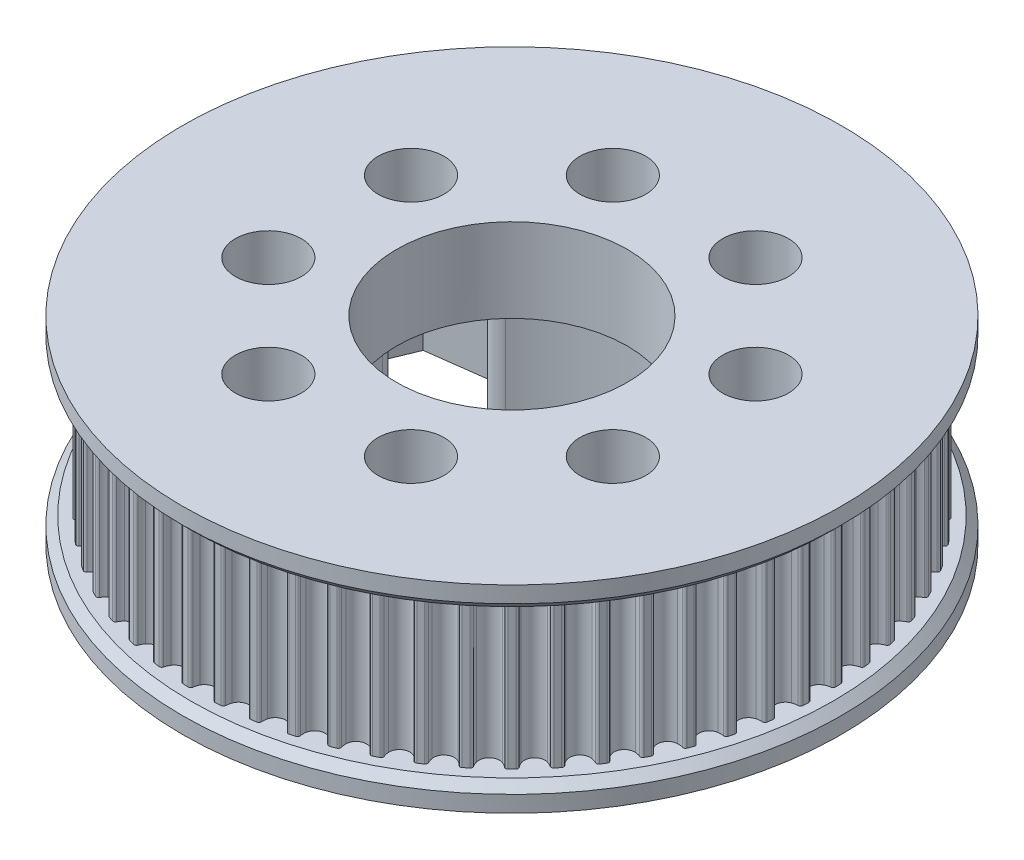
SolidWorks part; units mm, degrees
ref_plane "Front Plane" through (0, 0, 0) normal (0, 0, 1) x (1, 0, 0)
ref_plane "Top Plane" through (0, 0, 0) normal (0, 1, 0) x (1, 0, 0)
ref_plane "Right Plane" through (0, 0, 0) normal (1, 0, 0) x (0, 0, -1)
sketch "Sketch2" plane through (0, 0, 0) normal (0, 1, 0) x (1, 0, 0)
  arc A0 (0, -20) -> (0, 20) centre (0, 0) ccw
  arc A1 (0, 20) -> (0, -20) centre (0, 0) ccw
  arc A2 (-0.1312, 18.0334) -> (0, 18.0196) centre (0, 18.6496) ccw
  arc A3 (-1.8836, 17.9209) -> (-1.3573, 18.3322) centre (-1.9494, 18.5474) ccw
  arc A4 (-1.3573, 18.3322) -> (-1.2932, 18.6645) centre (-2.3677, 18.6994) ccw
  arc A5 (-0.6648, 18.6974) -> (-0.7174, 18.7921) centre (-0.8134, 18.6769) ccw
  arc A6 (-1.1525, 18.8093) -> (-1.2509, 18.7641) centre (-1.1433, 18.6596) ccw
  arc A7 (-1.2509, 18.7641) -> (-1.2932, 18.6645) centre (-1.1433, 18.6596) ccw
  arc A8 (-0.82, 18.8267) -> (-1.1525, 18.8093) centre (0, 0) ccw
  arc A9 (-0.7174, 18.7921) -> (-0.82, 18.8267) centre (-0.8134, 18.6769) ccw
  arc A10 (-0.6648, 18.6974) -> (-0.5664, 18.3737) centre (0.4001, 18.8445) ccw
  arc A11 (-0.5664, 18.3737) -> (-0.1312, 18.0334) centre (0, 18.6496) ccw
  arc A12 (1.7545, 17.9483) -> (1.8836, 17.9209) centre (1.9494, 18.5474) ccw
  arc A13 (0, 18.0196) -> (0.5664, 18.3737) centre (0, 18.6496) ccw
  arc A14 (0.5664, 18.3737) -> (0.6648, 18.6974) centre (-0.4001, 18.8445) ccw
  arc A15 (1.2932, 18.6645) -> (1.2509, 18.7641) centre (1.1433, 18.6596) ccw
  arc A16 (0.82, 18.8267) -> (0.7174, 18.7921) centre (0.8134, 18.6769) ccw
  arc A17 (0.7174, 18.7921) -> (0.6648, 18.6974) centre (0.8134, 18.6769) ccw
  arc A18 (1.1525, 18.8093) -> (0.82, 18.8267) centre (0, 0) ccw
  arc A19 (1.2509, 18.7641) -> (1.1525, 18.8093) centre (1.1433, 18.6596) ccw
  arc A20 (1.2932, 18.6645) -> (1.3573, 18.3322) centre (2.3677, 18.6994) ccw
  arc A21 (1.3573, 18.3322) -> (1.7545, 17.9483) centre (1.9494, 18.5474) ccw
  arc A22 (3.621, 17.6666) -> (3.7465, 17.6258) centre (3.8775, 18.2421) ccw
  arc A23 (1.8836, 17.9209) -> (2.4838, 18.2138) centre (1.9494, 18.5474) ccw
  arc A24 (2.4838, 18.2138) -> (2.6156, 18.5255) centre (1.5719, 18.7831) ccw
  arc A25 (3.2371, 18.4271) -> (3.2054, 18.5306) centre (3.0875, 18.4379) ccw
  arc A26 (2.7834, 18.6379) -> (2.6777, 18.6142) centre (2.7612, 18.4895) ccw
  arc A27 (2.6777, 18.6142) -> (2.6156, 18.5255) centre (2.7612, 18.4895) ccw
  arc A28 (3.1123, 18.5858) -> (2.7834, 18.6379) centre (0, 0) ccw
  arc A29 (3.2054, 18.5306) -> (3.1123, 18.5858) centre (3.0875, 18.4379) ccw
  arc A30 (3.2371, 18.4271) -> (3.2661, 18.0899) centre (4.3093, 18.3495) ccw
  arc A31 (3.2661, 18.0899) -> (3.621, 17.6666) centre (3.8775, 18.2421) ccw
  arc A32 (5.4478, 17.1913) -> (5.5684, 17.1377) centre (5.763, 17.7368) ccw
  arc A33 (3.7465, 17.6258) -> (4.3741, 17.8544) centre (3.8775, 18.2421) ccw
  arc A34 (4.3741, 17.8544) -> (4.5377, 18.1506) centre (3.5267, 18.5159) ccw
  arc A35 (5.1455, 17.9877) -> (5.1248, 18.094) centre (4.9979, 18.0141) ccw
  arc A36 (4.7163, 18.2449) -> (4.6088, 18.2323) centre (4.6788, 18.0996) ccw
  arc A37 (4.6088, 18.2323) -> (4.5377, 18.1506) centre (4.6788, 18.0996) ccw
  arc A38 (5.038, 18.1587) -> (4.7163, 18.2449) centre (0, 0) ccw
  arc A39 (5.1248, 18.094) -> (5.038, 18.1587) centre (4.9979, 18.0141) ccw
  arc A40 (5.1455, 17.9877) -> (5.1391, 17.6494) centre (6.2037, 17.7985) ccw
  arc A41 (5.1391, 17.6494) -> (5.4478, 17.1913) centre (5.763, 17.7368) ccw
  arc A42 (7.215, 16.5277) -> (7.3292, 16.4617) centre (7.5855, 17.0373) ccw
  arc A43 (5.5684, 17.1377) -> (6.2164, 17.2994) centre (5.763, 17.7368) ccw
  arc A44 (6.2164, 17.2994) -> (6.4101, 17.5768) centre (5.4428, 18.0458) ccw
  arc A45 (6.9976, 17.3513) -> (6.9881, 17.4592) centre (6.8535, 17.393) ccw
  arc A46 (6.5976, 17.6519) -> (6.4893, 17.6507) centre (6.5451, 17.5114) ccw
  arc A47 (6.4893, 17.6507) -> (6.4101, 17.5768) centre (6.5451, 17.5114) ccw
  arc A48 (6.9085, 17.5326) -> (6.5976, 17.6519) centre (0, 0) ccw
  arc A49 (6.9881, 17.4592) -> (6.9085, 17.5326) centre (6.8535, 17.393) ccw
  arc A50 (6.9976, 17.3513) -> (6.9558, 17.0156) centre (8.0302, 17.0526) ccw
  arc A51 (6.9558, 17.0156) -> (7.215, 16.5277) centre (7.5855, 17.0373) ccw
  arc A52 (8.9031, 15.683) -> (9.0098, 15.6054) centre (9.3248, 16.151) ccw
  arc A53 (7.3292, 16.4617) -> (7.9907, 16.5548) centre (7.5855, 17.0373) ccw
  arc A54 (7.9907, 16.5548) -> (8.2123, 16.8105) centre (7.2993, 17.378) ccw
  arc A55 (8.7729, 16.5248) -> (8.7748, 16.6331) centre (8.634, 16.5814) ccw
  arc A56 (8.4066, 16.8656) -> (8.2988, 16.8757) centre (8.3397, 16.7313) ccw
  arc A57 (8.2988, 16.8757) -> (8.2123, 16.8105) centre (8.3397, 16.7313) ccw
  arc A58 (8.7033, 16.7144) -> (8.4066, 16.8656) centre (0, 0) ccw
  arc A59 (8.7748, 16.6331) -> (8.7033, 16.7144) centre (8.634, 16.5814) ccw
  arc A60 (8.7729, 16.5248) -> (8.6964, 16.1953) centre (9.7687, 16.1198) ccw
  arc A61 (8.6964, 16.1953) -> (8.9031, 15.683) centre (9.3248, 16.151) ccw
  arc A62 (10.4936, 14.6665) -> (10.5917, 14.5782) centre (10.962, 15.0878) ccw
  arc A63 (9.0098, 15.6054) -> (9.6773, 15.6289) centre (9.3248, 16.151) ccw
  arc A64 (9.6773, 15.6289) -> (9.9245, 15.86) centre (9.0758, 16.5198) ccw
  arc A65 (10.4522, 15.5173) -> (10.4654, 15.6248) centre (10.3199, 15.588) ccw
  arc A66 (10.1235, 15.8945) -> (10.0173, 15.9157) centre (10.0429, 15.7679) ccw
  arc A67 (10.0173, 15.9157) -> (9.9245, 15.86) centre (10.0429, 15.7679) ccw
  arc A68 (10.4027, 15.7131) -> (10.1235, 15.8945) centre (0, 0) ccw
  arc A69 (10.4654, 15.6248) -> (10.4027, 15.7131) centre (10.3199, 15.588) ccw
  arc A70 (10.4522, 15.5173) -> (10.3416, 15.1975) centre (11.4002, 15.0104) ccw
  arc A71 (10.3416, 15.1975) -> (10.4936, 14.6665) centre (10.962, 15.0878) ccw
  arc A72 (11.9692, 13.4892) -> (12.0575, 13.3912) centre (12.479, 13.8593) ccw
  arc A73 (10.5917, 14.5782) -> (11.258, 14.5317) centre (10.962, 15.0878) ccw
  arc A74 (11.258, 14.5317) -> (11.5279, 14.7357) centre (10.7529, 15.4806) ccw
  arc A75 (12.0169, 14.3397) -> (12.0413, 14.4453) centre (11.8928, 14.4239) ccw
  arc A76 (11.7294, 14.7492) -> (11.6261, 14.7815) centre (11.6361, 14.6318) ccw
  arc A77 (11.6261, 14.7815) -> (11.5279, 14.7357) centre (11.6361, 14.6318) ccw
  arc A78 (11.9882, 14.5397) -> (11.7294, 14.7492) centre (0, 0) ccw
  arc A79 (12.0413, 14.4453) -> (11.9882, 14.5397) centre (11.8928, 14.4239) ccw
  arc A80 (12.0169, 14.3397) -> (11.8735, 14.0333) centre (12.9067, 13.7365) ccw
  arc A81 (11.8735, 14.0333) -> (11.9692, 13.4892) centre (12.479, 13.8593) ccw
  arc A82 (13.3136, 12.1642) -> (13.3912, 12.0575) centre (13.8593, 12.479) ccw
  arc A83 (12.0575, 13.3912) -> (12.7153, 13.2753) centre (12.479, 13.8593) ccw
  arc A84 (12.7153, 13.2753) -> (13.0051, 13.45) centre (12.3121, 14.2719) ccw
  arc A85 (13.45, 13.0051) -> (13.4852, 13.1075) centre (13.3353, 13.1018) ccw
  arc A86 (13.2069, 13.4423) -> (13.1075, 13.4852) centre (13.1018, 13.3353) ccw
  arc A87 (13.1075, 13.4852) -> (13.0051, 13.45) centre (13.1018, 13.3353) ccw
  arc A88 (13.4423, 13.2069) -> (13.2069, 13.4423) centre (0, 0) ccw
  arc A89 (13.4852, 13.1075) -> (13.4423, 13.2069) centre (13.3353, 13.1018) ccw
  arc A90 (13.45, 13.0051) -> (13.2753, 12.7153) centre (14.2719, 12.3121) ccw
  arc A91 (13.2753, 12.7153) -> (13.3136, 12.1642) centre (13.8593, 12.479) ccw
  arc A92 (14.5122, 10.7059) -> (14.5782, 10.5917) centre (15.0878, 10.962) ccw
  arc A93 (13.3912, 12.0575) -> (14.0333, 11.8735) centre (13.8593, 12.479) ccw
  arc A94 (14.0333, 11.8735) -> (14.3397, 12.0169) centre (13.7365, 12.9067) ccw
  arc A95 (14.7357, 11.5279) -> (14.7815, 11.6261) centre (14.6318, 11.6361) ccw
  arc A96 (14.5397, 11.9882) -> (14.4453, 12.0413) centre (14.4239, 11.8928) ccw
  arc A97 (14.4453, 12.0413) -> (14.3397, 12.0169) centre (14.4239, 11.8928) ccw
  arc A98 (14.7492, 11.7294) -> (14.5397, 11.9882) centre (0, 0) ccw
  arc A99 (14.7815, 11.6261) -> (14.7492, 11.7294) centre (14.6318, 11.6361) ccw
  arc A100 (14.7357, 11.5279) -> (14.5317, 11.258) centre (15.4806, 10.7529) ccw
  arc A101 (14.5317, 11.258) -> (14.5122, 10.7059) centre (15.0878, 10.962) ccw
  arc A102 (15.5518, 9.1304) -> (15.6054, 9.0098) centre (16.151, 9.3248) ccw
  arc A103 (14.5782, 10.5917) -> (15.1975, 10.3416) centre (15.0878, 10.962) ccw
  arc A104 (15.1975, 10.3416) -> (15.5173, 10.4522) centre (15.0104, 11.4002) ccw
  arc A105 (15.86, 9.9245) -> (15.9157, 10.0173) centre (15.7679, 10.0429) ccw
  arc A106 (15.7131, 10.4027) -> (15.6248, 10.4654) centre (15.588, 10.3199) ccw
  arc A107 (15.6248, 10.4654) -> (15.5173, 10.4522) centre (15.588, 10.3199) ccw
  arc A108 (15.8945, 10.1235) -> (15.7131, 10.4027) centre (0, 0) ccw
  arc A109 (15.9157, 10.0173) -> (15.8945, 10.1235) centre (15.7679, 10.0429) ccw
  arc A110 (15.86, 9.9245) -> (15.6289, 9.6773) centre (16.5198, 9.0758) ccw
  arc A111 (15.6289, 9.6773) -> (15.5518, 9.1304) centre (16.151, 9.3248) ccw
  arc A112 (16.421, 7.4547) -> (16.4617, 7.3292) centre (17.0373, 7.5855) ccw
  arc A113 (15.6054, 9.0098) -> (16.1953, 8.6964) centre (16.151, 9.3248) ccw
  arc A114 (16.1953, 8.6964) -> (16.5248, 8.7729) centre (16.1198, 9.7687) ccw
  arc A115 (16.8105, 8.2123) -> (16.8757, 8.2988) centre (16.7313, 8.3397) ccw
  arc A116 (16.7144, 8.7033) -> (16.6331, 8.7748) centre (16.5814, 8.634) ccw
  arc A117 (16.6331, 8.7748) -> (16.5248, 8.7729) centre (16.5814, 8.634) ccw
  arc A118 (16.8656, 8.4066) -> (16.7144, 8.7033) centre (0, 0) ccw
  arc A119 (16.8757, 8.2988) -> (16.8656, 8.4066) centre (16.7313, 8.3397) ccw
  arc A120 (16.8105, 8.2123) -> (16.5548, 7.9907) centre (17.378, 7.2993) ccw
  arc A121 (16.5548, 7.9907) -> (16.421, 7.4547) centre (17.0373, 7.5855) ccw
  arc A122 (17.1102, 5.6974) -> (17.1377, 5.5684) centre (17.7368, 5.763) ccw
  arc A123 (16.4617, 7.3292) -> (17.0156, 6.9558) centre (17.0373, 7.5855) ccw
  arc A124 (17.0156, 6.9558) -> (17.3513, 6.9976) centre (17.0526, 8.0302) ccw
  arc A125 (17.5768, 6.4101) -> (17.6507, 6.4893) centre (17.5114, 6.5451) ccw
  arc A126 (17.5326, 6.9085) -> (17.4592, 6.9881) centre (17.393, 6.8535) ccw
  arc A127 (17.4592, 6.9881) -> (17.3513, 6.9976) centre (17.393, 6.8535) ccw
  arc A128 (17.6519, 6.5976) -> (17.5326, 6.9085) centre (0, 0) ccw
  arc A129 (17.6507, 6.4893) -> (17.6519, 6.5976) centre (17.5114, 6.5451) ccw
  arc A130 (17.5768, 6.4101) -> (17.2994, 6.2164) centre (18.0458, 5.4428) ccw
  arc A131 (17.2994, 6.2164) -> (17.1102, 5.6974) centre (17.7368, 5.763) ccw
  arc A132 (17.6121, 3.8777) -> (17.6258, 3.7465) centre (18.2421, 3.8775) ccw
  arc A133 (17.1377, 5.5684) -> (17.6494, 5.1391) centre (17.7368, 5.763) ccw
  arc A134 (17.6494, 5.1391) -> (17.9877, 5.1455) centre (17.7985, 6.2037) ccw
  arc A135 (18.1506, 4.5377) -> (18.2323, 4.6088) centre (18.0996, 4.6788) ccw
  arc A136 (18.1587, 5.038) -> (18.094, 5.1248) centre (18.0141, 4.9979) ccw
  arc A137 (18.094, 5.1248) -> (17.9877, 5.1455) centre (18.0141, 4.9979) ccw
  arc A138 (18.2449, 4.7163) -> (18.1587, 5.038) centre (0, 0) ccw
  arc A139 (18.2323, 4.6088) -> (18.2449, 4.7163) centre (18.0996, 4.6788) ccw
  arc A140 (18.1506, 4.5377) -> (17.8544, 4.3741) centre (18.5159, 3.5267) ccw
  arc A141 (17.8544, 4.3741) -> (17.6121, 3.8777) centre (18.2421, 3.8775) ccw
  arc A142 (17.9209, 2.0155) -> (17.9209, 1.8836) centre (18.5474, 1.9494) ccw
  arc A143 (17.6258, 3.7465) -> (18.0899, 3.2661) centre (18.2421, 3.8775) ccw
  arc A144 (18.0899, 3.2661) -> (18.4271, 3.2371) centre (18.3495, 4.3093) ccw
  arc A145 (18.5255, 2.6156) -> (18.6142, 2.6777) centre (18.4895, 2.7612) ccw
  arc A146 (18.5858, 3.1123) -> (18.5306, 3.2054) centre (18.4379, 3.0875) ccw
  arc A147 (18.5306, 3.2054) -> (18.4271, 3.2371) centre (18.4379, 3.0875) ccw
  arc A148 (18.6379, 2.7834) -> (18.5858, 3.1123) centre (0, 0) ccw
  arc A149 (18.6142, 2.6777) -> (18.6379, 2.7834) centre (18.4895, 2.7612) ccw
  arc A150 (18.5255, 2.6156) -> (18.2138, 2.4838) centre (18.7831, 1.5719) ccw
  arc A151 (18.2138, 2.4838) -> (17.9209, 2.0155) centre (18.5474, 1.9494) ccw
  arc A152 (18.0334, 0.1312) -> (18.0196, 0) centre (18.6496, 0) ccw
  arc A153 (17.9209, 1.8836) -> (18.3322, 1.3573) centre (18.5474, 1.9494) ccw
  arc A154 (18.3322, 1.3573) -> (18.6645, 1.2932) centre (18.6994, 2.3677) ccw
  arc A155 (18.6974, 0.6648) -> (18.7921, 0.7174) centre (18.6769, 0.8134) ccw
  arc A156 (18.8093, 1.1525) -> (18.7641, 1.2509) centre (18.6596, 1.1433) ccw
  arc A157 (18.7641, 1.2509) -> (18.6645, 1.2932) centre (18.6596, 1.1433) ccw
  arc A158 (18.8267, 0.82) -> (18.8093, 1.1525) centre (0, 0) ccw
  arc A159 (18.7921, 0.7174) -> (18.8267, 0.82) centre (18.6769, 0.8134) ccw
  arc A160 (18.6974, 0.6648) -> (18.3737, 0.5664) centre (18.8445, -0.4001) ccw
  arc A161 (18.3737, 0.5664) -> (18.0334, 0.1312) centre (18.6496, 0) ccw
  arc A162 (17.9483, -1.7545) -> (17.9209, -1.8836) centre (18.5474, -1.9494) ccw
  arc A163 (18.0196, 0) -> (18.3737, -0.5664) centre (18.6496, 0) ccw
  arc A164 (18.3737, -0.5664) -> (18.6974, -0.6648) centre (18.8445, 0.4001) ccw
  arc A165 (18.6645, -1.2932) -> (18.7641, -1.2509) centre (18.6596, -1.1433) ccw
  arc A166 (18.8267, -0.82) -> (18.7921, -0.7174) centre (18.6769, -0.8134) ccw
  arc A167 (18.7921, -0.7174) -> (18.6974, -0.6648) centre (18.6769, -0.8134) ccw
  arc A168 (18.8093, -1.1525) -> (18.8267, -0.82) centre (0, 0) ccw
  arc A169 (18.7641, -1.2509) -> (18.8093, -1.1525) centre (18.6596, -1.1433) ccw
  arc A170 (18.6645, -1.2932) -> (18.3322, -1.3573) centre (18.6994, -2.3677) ccw
  arc A171 (18.3322, -1.3573) -> (17.9483, -1.7545) centre (18.5474, -1.9494) ccw
  arc A172 (17.6666, -3.621) -> (17.6258, -3.7465) centre (18.2421, -3.8775) ccw
  arc A173 (17.9209, -1.8836) -> (18.2138, -2.4838) centre (18.5474, -1.9494) ccw
  arc A174 (18.2138, -2.4838) -> (18.5255, -2.6156) centre (18.7831, -1.5719) ccw
  arc A175 (18.4271, -3.2371) -> (18.5306, -3.2054) centre (18.4379, -3.0875) ccw
  arc A176 (18.6379, -2.7834) -> (18.6142, -2.6777) centre (18.4895, -2.7612) ccw
  arc A177 (18.6142, -2.6777) -> (18.5255, -2.6156) centre (18.4895, -2.7612) ccw
  arc A178 (18.5858, -3.1123) -> (18.6379, -2.7834) centre (0, 0) ccw
  arc A179 (18.5306, -3.2054) -> (18.5858, -3.1123) centre (18.4379, -3.0875) ccw
  arc A180 (18.4271, -3.2371) -> (18.0899, -3.2661) centre (18.3495, -4.3093) ccw
  arc A181 (18.0899, -3.2661) -> (17.6666, -3.621) centre (18.2421, -3.8775) ccw
  arc A182 (17.1913, -5.4478) -> (17.1377, -5.5684) centre (17.7368, -5.763) ccw
  arc A183 (17.6258, -3.7465) -> (17.8544, -4.3741) centre (18.2421, -3.8775) ccw
  arc A184 (17.8544, -4.3741) -> (18.1506, -4.5377) centre (18.5159, -3.5267) ccw
  arc A185 (17.9877, -5.1455) -> (18.094, -5.1248) centre (18.0141, -4.9979) ccw
  arc A186 (18.2449, -4.7163) -> (18.2323, -4.6088) centre (18.0996, -4.6788) ccw
  arc A187 (18.2323, -4.6088) -> (18.1506, -4.5377) centre (18.0996, -4.6788) ccw
  arc A188 (18.1587, -5.038) -> (18.2449, -4.7163) centre (0, 0) ccw
  arc A189 (18.094, -5.1248) -> (18.1587, -5.038) centre (18.0141, -4.9979) ccw
  arc A190 (17.9877, -5.1455) -> (17.6494, -5.1391) centre (17.7985, -6.2037) ccw
  arc A191 (17.6494, -5.1391) -> (17.1913, -5.4478) centre (17.7368, -5.763) ccw
  arc A192 (16.5277, -7.215) -> (16.4617, -7.3292) centre (17.0373, -7.5855) ccw
  arc A193 (17.1377, -5.5684) -> (17.2994, -6.2164) centre (17.7368, -5.763) ccw
  arc A194 (17.2994, -6.2164) -> (17.5768, -6.4101) centre (18.0458, -5.4428) ccw
  arc A195 (17.3513, -6.9976) -> (17.4592, -6.9881) centre (17.393, -6.8535) ccw
  arc A196 (17.6519, -6.5976) -> (17.6507, -6.4893) centre (17.5114, -6.5451) ccw
  arc A197 (17.6507, -6.4893) -> (17.5768, -6.4101) centre (17.5114, -6.5451) ccw
  arc A198 (17.5326, -6.9085) -> (17.6519, -6.5976) centre (0, 0) ccw
  arc A199 (17.4592, -6.9881) -> (17.5326, -6.9085) centre (17.393, -6.8535) ccw
  arc A200 (17.3513, -6.9976) -> (17.0156, -6.9558) centre (17.0526, -8.0302) ccw
  arc A201 (17.0156, -6.9558) -> (16.5277, -7.215) centre (17.0373, -7.5855) ccw
  arc A202 (15.683, -8.9031) -> (15.6054, -9.0098) centre (16.151, -9.3248) ccw
  arc A203 (16.4617, -7.3292) -> (16.5548, -7.9907) centre (17.0373, -7.5855) ccw
  arc A204 (16.5548, -7.9907) -> (16.8105, -8.2123) centre (17.378, -7.2993) ccw
  arc A205 (16.5248, -8.7729) -> (16.6331, -8.7748) centre (16.5814, -8.634) ccw
  arc A206 (16.8656, -8.4066) -> (16.8757, -8.2988) centre (16.7313, -8.3397) ccw
  arc A207 (16.8757, -8.2988) -> (16.8105, -8.2123) centre (16.7313, -8.3397) ccw
  arc A208 (16.7144, -8.7033) -> (16.8656, -8.4066) centre (0, 0) ccw
  arc A209 (16.6331, -8.7748) -> (16.7144, -8.7033) centre (16.5814, -8.634) ccw
  arc A210 (16.5248, -8.7729) -> (16.1953, -8.6964) centre (16.1198, -9.7687) ccw
  arc A211 (16.1953, -8.6964) -> (15.683, -8.9031) centre (16.151, -9.3248) ccw
  arc A212 (14.6665, -10.4936) -> (14.5782, -10.5917) centre (15.0878, -10.962) ccw
  arc A213 (15.6054, -9.0098) -> (15.6289, -9.6773) centre (16.151, -9.3248) ccw
  arc A214 (15.6289, -9.6773) -> (15.86, -9.9245) centre (16.5198, -9.0758) ccw
  arc A215 (15.5173, -10.4522) -> (15.6248, -10.4654) centre (15.588, -10.3199) ccw
  arc A216 (15.8945, -10.1235) -> (15.9157, -10.0173) centre (15.7679, -10.0429) ccw
  arc A217 (15.9157, -10.0173) -> (15.86, -9.9245) centre (15.7679, -10.0429) ccw
  arc A218 (15.7131, -10.4027) -> (15.8945, -10.1235) centre (0, 0) ccw
  arc A219 (15.6248, -10.4654) -> (15.7131, -10.4027) centre (15.588, -10.3199) ccw
  arc A220 (15.5173, -10.4522) -> (15.1975, -10.3416) centre (15.0104, -11.4002) ccw
  arc A221 (15.1975, -10.3416) -> (14.6665, -10.4936) centre (15.0878, -10.962) ccw
  arc A222 (13.4892, -11.9692) -> (13.3912, -12.0575) centre (13.8593, -12.479) ccw
  arc A223 (14.5782, -10.5917) -> (14.5317, -11.258) centre (15.0878, -10.962) ccw
  arc A224 (14.5317, -11.258) -> (14.7357, -11.5279) centre (15.4806, -10.7529) ccw
  arc A225 (14.3397, -12.0169) -> (14.4453, -12.0413) centre (14.4239, -11.8928) ccw
  arc A226 (14.7492, -11.7294) -> (14.7815, -11.6261) centre (14.6318, -11.6361) ccw
  arc A227 (14.7815, -11.6261) -> (14.7357, -11.5279) centre (14.6318, -11.6361) ccw
  arc A228 (14.5397, -11.9882) -> (14.7492, -11.7294) centre (0, 0) ccw
  arc A229 (14.4453, -12.0413) -> (14.5397, -11.9882) centre (14.4239, -11.8928) ccw
  arc A230 (14.3397, -12.0169) -> (14.0333, -11.8735) centre (13.7365, -12.9067) ccw
  arc A231 (14.0333, -11.8735) -> (13.4892, -11.9692) centre (13.8593, -12.479) ccw
  arc A232 (12.1642, -13.3136) -> (12.0575, -13.3912) centre (12.479, -13.8593) ccw
  arc A233 (13.3912, -12.0575) -> (13.2753, -12.7153) centre (13.8593, -12.479) ccw
  arc A234 (13.2753, -12.7153) -> (13.45, -13.0051) centre (14.2719, -12.3121) ccw
  arc A235 (13.0051, -13.45) -> (13.1075, -13.4852) centre (13.1018, -13.3353) ccw
  arc A236 (13.4423, -13.2069) -> (13.4852, -13.1075) centre (13.3353, -13.1018) ccw
  arc A237 (13.4852, -13.1075) -> (13.45, -13.0051) centre (13.3353, -13.1018) ccw
  arc A238 (13.2069, -13.4423) -> (13.4423, -13.2069) centre (0, 0) ccw
  arc A239 (13.1075, -13.4852) -> (13.2069, -13.4423) centre (13.1018, -13.3353) ccw
  arc A240 (13.0051, -13.45) -> (12.7153, -13.2753) centre (12.3121, -14.2719) ccw
  arc A241 (12.7153, -13.2753) -> (12.1642, -13.3136) centre (12.479, -13.8593) ccw
  arc A242 (10.7059, -14.5122) -> (10.5917, -14.5782) centre (10.962, -15.0878) ccw
  arc A243 (12.0575, -13.3912) -> (11.8735, -14.0333) centre (12.479, -13.8593) ccw
  arc A244 (11.8735, -14.0333) -> (12.0169, -14.3397) centre (12.9067, -13.7365) ccw
  arc A245 (11.5279, -14.7357) -> (11.6261, -14.7815) centre (11.6361, -14.6318) ccw
  arc A246 (11.9882, -14.5397) -> (12.0413, -14.4453) centre (11.8928, -14.4239) ccw
  arc A247 (12.0413, -14.4453) -> (12.0169, -14.3397) centre (11.8928, -14.4239) ccw
  arc A248 (11.7294, -14.7492) -> (11.9882, -14.5397) centre (0, 0) ccw
  arc A249 (11.6261, -14.7815) -> (11.7294, -14.7492) centre (11.6361, -14.6318) ccw
  arc A250 (11.5279, -14.7357) -> (11.258, -14.5317) centre (10.7529, -15.4806) ccw
  arc A251 (11.258, -14.5317) -> (10.7059, -14.5122) centre (10.962, -15.0878) ccw
  arc A252 (9.1304, -15.5518) -> (9.0098, -15.6054) centre (9.3248, -16.151) ccw
  arc A253 (10.5917, -14.5782) -> (10.3416, -15.1975) centre (10.962, -15.0878) ccw
  arc A254 (10.3416, -15.1975) -> (10.4522, -15.5173) centre (11.4002, -15.0104) ccw
  arc A255 (9.9245, -15.86) -> (10.0173, -15.9157) centre (10.0429, -15.7679) ccw
  arc A256 (10.4027, -15.7131) -> (10.4654, -15.6248) centre (10.3199, -15.588) ccw
  arc A257 (10.4654, -15.6248) -> (10.4522, -15.5173) centre (10.3199, -15.588) ccw
  arc A258 (10.1235, -15.8945) -> (10.4027, -15.7131) centre (0, 0) ccw
  arc A259 (10.0173, -15.9157) -> (10.1235, -15.8945) centre (10.0429, -15.7679) ccw
  arc A260 (9.9245, -15.86) -> (9.6773, -15.6289) centre (9.0758, -16.5198) ccw
  arc A261 (9.6773, -15.6289) -> (9.1304, -15.5518) centre (9.3248, -16.151) ccw
  arc A262 (7.4547, -16.421) -> (7.3292, -16.4617) centre (7.5855, -17.0373) ccw
  arc A263 (9.0098, -15.6054) -> (8.6964, -16.1953) centre (9.3248, -16.151) ccw
  arc A264 (8.6964, -16.1953) -> (8.7729, -16.5248) centre (9.7687, -16.1198) ccw
  arc A265 (8.2123, -16.8105) -> (8.2988, -16.8757) centre (8.3397, -16.7313) ccw
  arc A266 (8.7033, -16.7144) -> (8.7748, -16.6331) centre (8.634, -16.5814) ccw
  arc A267 (8.7748, -16.6331) -> (8.7729, -16.5248) centre (8.634, -16.5814) ccw
  arc A268 (8.4066, -16.8656) -> (8.7033, -16.7144) centre (0, 0) ccw
  arc A269 (8.2988, -16.8757) -> (8.4066, -16.8656) centre (8.3397, -16.7313) ccw
  arc A270 (8.2123, -16.8105) -> (7.9907, -16.5548) centre (7.2993, -17.378) ccw
  arc A271 (7.9907, -16.5548) -> (7.4547, -16.421) centre (7.5855, -17.0373) ccw
  arc A272 (5.6974, -17.1102) -> (5.5684, -17.1377) centre (5.763, -17.7368) ccw
  arc A273 (7.3292, -16.4617) -> (6.9558, -17.0156) centre (7.5855, -17.0373) ccw
  arc A274 (6.9558, -17.0156) -> (6.9976, -17.3513) centre (8.0302, -17.0526) ccw
  arc A275 (6.4101, -17.5768) -> (6.4893, -17.6507) centre (6.5451, -17.5114) ccw
  arc A276 (6.9085, -17.5326) -> (6.9881, -17.4592) centre (6.8535, -17.393) ccw
  arc A277 (6.9881, -17.4592) -> (6.9976, -17.3513) centre (6.8535, -17.393) ccw
  arc A278 (6.5976, -17.6519) -> (6.9085, -17.5326) centre (0, 0) ccw
  arc A279 (6.4893, -17.6507) -> (6.5976, -17.6519) centre (6.5451, -17.5114) ccw
  arc A280 (6.4101, -17.5768) -> (6.2164, -17.2994) centre (5.4428, -18.0458) ccw
  arc A281 (6.2164, -17.2994) -> (5.6974, -17.1102) centre (5.763, -17.7368) ccw
  arc A282 (3.8777, -17.6121) -> (3.7465, -17.6258) centre (3.8775, -18.2421) ccw
  arc A283 (5.5684, -17.1377) -> (5.1391, -17.6494) centre (5.763, -17.7368) ccw
  arc A284 (5.1391, -17.6494) -> (5.1455, -17.9877) centre (6.2037, -17.7985) ccw
  arc A285 (4.5377, -18.1506) -> (4.6088, -18.2323) centre (4.6788, -18.0996) ccw
  arc A286 (5.038, -18.1587) -> (5.1248, -18.094) centre (4.9979, -18.0141) ccw
  arc A287 (5.1248, -18.094) -> (5.1455, -17.9877) centre (4.9979, -18.0141) ccw
  arc A288 (4.7163, -18.2449) -> (5.038, -18.1587) centre (0, 0) ccw
  arc A289 (4.6088, -18.2323) -> (4.7163, -18.2449) centre (4.6788, -18.0996) ccw
  arc A290 (4.5377, -18.1506) -> (4.3741, -17.8544) centre (3.5267, -18.5159) ccw
  arc A291 (4.3741, -17.8544) -> (3.8777, -17.6121) centre (3.8775, -18.2421) ccw
  arc A292 (2.0155, -17.9209) -> (1.8836, -17.9209) centre (1.9494, -18.5474) ccw
  arc A293 (3.7465, -17.6258) -> (3.2661, -18.0899) centre (3.8775, -18.2421) ccw
  arc A294 (3.2661, -18.0899) -> (3.2371, -18.4271) centre (4.3093, -18.3495) ccw
  arc A295 (2.6156, -18.5255) -> (2.6777, -18.6142) centre (2.7612, -18.4895) ccw
  arc A296 (3.1123, -18.5858) -> (3.2054, -18.5306) centre (3.0875, -18.4379) ccw
  arc A297 (3.2054, -18.5306) -> (3.2371, -18.4271) centre (3.0875, -18.4379) ccw
  arc A298 (2.7834, -18.6379) -> (3.1123, -18.5858) centre (0, 0) ccw
  arc A299 (2.6777, -18.6142) -> (2.7834, -18.6379) centre (2.7612, -18.4895) ccw
  arc A300 (2.6156, -18.5255) -> (2.4838, -18.2138) centre (1.5719, -18.7831) ccw
  arc A301 (2.4838, -18.2138) -> (2.0155, -17.9209) centre (1.9494, -18.5474) ccw
  arc A302 (0.1312, -18.0334) -> (0, -18.0196) centre (0, -18.6496) ccw
  arc A303 (1.8836, -17.9209) -> (1.3573, -18.3322) centre (1.9494, -18.5474) ccw
  arc A304 (1.3573, -18.3322) -> (1.2932, -18.6645) centre (2.3677, -18.6994) ccw
  arc A305 (0.6648, -18.6974) -> (0.7174, -18.7921) centre (0.8134, -18.6769) ccw
  arc A306 (1.1525, -18.8093) -> (1.2509, -18.7641) centre (1.1433, -18.6596) ccw
  arc A307 (1.2509, -18.7641) -> (1.2932, -18.6645) centre (1.1433, -18.6596) ccw
  arc A308 (0.82, -18.8267) -> (1.1525, -18.8093) centre (0, 0) ccw
  arc A309 (0.7174, -18.7921) -> (0.82, -18.8267) centre (0.8134, -18.6769) ccw
  arc A310 (0.6648, -18.6974) -> (0.5664, -18.3737) centre (-0.4001, -18.8445) ccw
  arc A311 (0.5664, -18.3737) -> (0.1312, -18.0334) centre (0, -18.6496) ccw
  arc A312 (-1.7545, -17.9483) -> (-1.8836, -17.9209) centre (-1.9494, -18.5474) ccw
  arc A313 (0, -18.0196) -> (-0.5664, -18.3737) centre (0, -18.6496) ccw
  arc A314 (-0.5664, -18.3737) -> (-0.6648, -18.6974) centre (0.4001, -18.8445) ccw
  arc A315 (-1.2932, -18.6645) -> (-1.2509, -18.7641) centre (-1.1433, -18.6596) ccw
  arc A316 (-0.82, -18.8267) -> (-0.7174, -18.7921) centre (-0.8134, -18.6769) ccw
  arc A317 (-0.7174, -18.7921) -> (-0.6648, -18.6974) centre (-0.8134, -18.6769) ccw
  arc A318 (-1.1525, -18.8093) -> (-0.82, -18.8267) centre (0, 0) ccw
  arc A319 (-1.2509, -18.7641) -> (-1.1525, -18.8093) centre (-1.1433, -18.6596) ccw
  arc A320 (-1.2932, -18.6645) -> (-1.3573, -18.3322) centre (-2.3677, -18.6994) ccw
  arc A321 (-1.3573, -18.3322) -> (-1.7545, -17.9483) centre (-1.9494, -18.5474) ccw
  arc A322 (-3.621, -17.6666) -> (-3.7465, -17.6258) centre (-3.8775, -18.2421) ccw
  arc A323 (-1.8836, -17.9209) -> (-2.4838, -18.2138) centre (-1.9494, -18.5474) ccw
  arc A324 (-2.4838, -18.2138) -> (-2.6156, -18.5255) centre (-1.5719, -18.7831) ccw
  arc A325 (-3.2371, -18.4271) -> (-3.2054, -18.5306) centre (-3.0875, -18.4379) ccw
  arc A326 (-2.7834, -18.6379) -> (-2.6777, -18.6142) centre (-2.7612, -18.4895) ccw
  arc A327 (-2.6777, -18.6142) -> (-2.6156, -18.5255) centre (-2.7612, -18.4895) ccw
  arc A328 (-3.1123, -18.5858) -> (-2.7834, -18.6379) centre (0, 0) ccw
  arc A329 (-3.2054, -18.5306) -> (-3.1123, -18.5858) centre (-3.0875, -18.4379) ccw
  arc A330 (-3.2371, -18.4271) -> (-3.2661, -18.0899) centre (-4.3093, -18.3495) ccw
  arc A331 (-3.2661, -18.0899) -> (-3.621, -17.6666) centre (-3.8775, -18.2421) ccw
  arc A332 (-5.4478, -17.1913) -> (-5.5684, -17.1377) centre (-5.763, -17.7368) ccw
  arc A333 (-3.7465, -17.6258) -> (-4.3741, -17.8544) centre (-3.8775, -18.2421) ccw
  arc A334 (-4.3741, -17.8544) -> (-4.5377, -18.1506) centre (-3.5267, -18.5159) ccw
  arc A335 (-5.1455, -17.9877) -> (-5.1248, -18.094) centre (-4.9979, -18.0141) ccw
  arc A336 (-4.7163, -18.2449) -> (-4.6088, -18.2323) centre (-4.6788, -18.0996) ccw
  arc A337 (-4.6088, -18.2323) -> (-4.5377, -18.1506) centre (-4.6788, -18.0996) ccw
  arc A338 (-5.038, -18.1587) -> (-4.7163, -18.2449) centre (0, 0) ccw
  arc A339 (-5.1248, -18.094) -> (-5.038, -18.1587) centre (-4.9979, -18.0141) ccw
  arc A340 (-5.1455, -17.9877) -> (-5.1391, -17.6494) centre (-6.2037, -17.7985) ccw
  arc A341 (-5.1391, -17.6494) -> (-5.4478, -17.1913) centre (-5.763, -17.7368) ccw
  arc A342 (-7.215, -16.5277) -> (-7.3292, -16.4617) centre (-7.5855, -17.0373) ccw
  arc A343 (-5.5684, -17.1377) -> (-6.2164, -17.2994) centre (-5.763, -17.7368) ccw
  arc A344 (-6.2164, -17.2994) -> (-6.4101, -17.5768) centre (-5.4428, -18.0458) ccw
  arc A345 (-6.9976, -17.3513) -> (-6.9881, -17.4592) centre (-6.8535, -17.393) ccw
  arc A346 (-6.5976, -17.6519) -> (-6.4893, -17.6507) centre (-6.5451, -17.5114) ccw
  arc A347 (-6.4893, -17.6507) -> (-6.4101, -17.5768) centre (-6.5451, -17.5114) ccw
  arc A348 (-6.9085, -17.5326) -> (-6.5976, -17.6519) centre (0, 0) ccw
  arc A349 (-6.9881, -17.4592) -> (-6.9085, -17.5326) centre (-6.8535, -17.393) ccw
  arc A350 (-6.9976, -17.3513) -> (-6.9558, -17.0156) centre (-8.0302, -17.0526) ccw
  arc A351 (-6.9558, -17.0156) -> (-7.215, -16.5277) centre (-7.5855, -17.0373) ccw
  arc A352 (-8.9031, -15.683) -> (-9.0098, -15.6054) centre (-9.3248, -16.151) ccw
  arc A353 (-7.3292, -16.4617) -> (-7.9907, -16.5548) centre (-7.5855, -17.0373) ccw
  arc A354 (-7.9907, -16.5548) -> (-8.2123, -16.8105) centre (-7.2993, -17.378) ccw
  arc A355 (-8.7729, -16.5248) -> (-8.7748, -16.6331) centre (-8.634, -16.5814) ccw
  arc A356 (-8.4066, -16.8656) -> (-8.2988, -16.8757) centre (-8.3397, -16.7313) ccw
  arc A357 (-8.2988, -16.8757) -> (-8.2123, -16.8105) centre (-8.3397, -16.7313) ccw
  arc A358 (-8.7033, -16.7144) -> (-8.4066, -16.8656) centre (0, 0) ccw
  arc A359 (-8.7748, -16.6331) -> (-8.7033, -16.7144) centre (-8.634, -16.5814) ccw
  arc A360 (-8.7729, -16.5248) -> (-8.6964, -16.1953) centre (-9.7687, -16.1198) ccw
  arc A361 (-8.6964, -16.1953) -> (-8.9031, -15.683) centre (-9.3248, -16.151) ccw
  arc A362 (-10.4936, -14.6665) -> (-10.5917, -14.5782) centre (-10.962, -15.0878) ccw
  arc A363 (-9.0098, -15.6054) -> (-9.6773, -15.6289) centre (-9.3248, -16.151) ccw
  arc A364 (-9.6773, -15.6289) -> (-9.9245, -15.86) centre (-9.0758, -16.5198) ccw
  arc A365 (-10.4522, -15.5173) -> (-10.4654, -15.6248) centre (-10.3199, -15.588) ccw
  arc A366 (-10.1235, -15.8945) -> (-10.0173, -15.9157) centre (-10.0429, -15.7679) ccw
  arc A367 (-10.0173, -15.9157) -> (-9.9245, -15.86) centre (-10.0429, -15.7679) ccw
  arc A368 (-10.4027, -15.7131) -> (-10.1235, -15.8945) centre (0, 0) ccw
  arc A369 (-10.4654, -15.6248) -> (-10.4027, -15.7131) centre (-10.3199, -15.588) ccw
  arc A370 (-10.4522, -15.5173) -> (-10.3416, -15.1975) centre (-11.4002, -15.0104) ccw
  arc A371 (-10.3416, -15.1975) -> (-10.4936, -14.6665) centre (-10.962, -15.0878) ccw
  arc A372 (-11.9692, -13.4892) -> (-12.0575, -13.3912) centre (-12.479, -13.8593) ccw
  arc A373 (-10.5917, -14.5782) -> (-11.258, -14.5317) centre (-10.962, -15.0878) ccw
  arc A374 (-11.258, -14.5317) -> (-11.5279, -14.7357) centre (-10.7529, -15.4806) ccw
  arc A375 (-12.0169, -14.3397) -> (-12.0413, -14.4453) centre (-11.8928, -14.4239) ccw
  arc A376 (-11.7294, -14.7492) -> (-11.6261, -14.7815) centre (-11.6361, -14.6318) ccw
  arc A377 (-11.6261, -14.7815) -> (-11.5279, -14.7357) centre (-11.6361, -14.6318) ccw
  arc A378 (-11.9882, -14.5397) -> (-11.7294, -14.7492) centre (0, 0) ccw
  arc A379 (-12.0413, -14.4453) -> (-11.9882, -14.5397) centre (-11.8928, -14.4239) ccw
  arc A380 (-12.0169, -14.3397) -> (-11.8735, -14.0333) centre (-12.9067, -13.7365) ccw
  arc A381 (-11.8735, -14.0333) -> (-11.9692, -13.4892) centre (-12.479, -13.8593) ccw
  arc A382 (-13.3136, -12.1642) -> (-13.3912, -12.0575) centre (-13.8593, -12.479) ccw
  arc A383 (-12.0575, -13.3912) -> (-12.7153, -13.2753) centre (-12.479, -13.8593) ccw
  arc A384 (-12.7153, -13.2753) -> (-13.0051, -13.45) centre (-12.3121, -14.2719) ccw
  arc A385 (-13.45, -13.0051) -> (-13.4852, -13.1075) centre (-13.3353, -13.1018) ccw
  arc A386 (-13.2069, -13.4423) -> (-13.1075, -13.4852) centre (-13.1018, -13.3353) ccw
  arc A387 (-13.1075, -13.4852) -> (-13.0051, -13.45) centre (-13.1018, -13.3353) ccw
  arc A388 (-13.4423, -13.2069) -> (-13.2069, -13.4423) centre (0, 0) ccw
  arc A389 (-13.4852, -13.1075) -> (-13.4423, -13.2069) centre (-13.3353, -13.1018) ccw
  arc A390 (-13.45, -13.0051) -> (-13.2753, -12.7153) centre (-14.2719, -12.3121) ccw
  arc A391 (-13.2753, -12.7153) -> (-13.3136, -12.1642) centre (-13.8593, -12.479) ccw
  arc A392 (-14.5122, -10.7059) -> (-14.5782, -10.5917) centre (-15.0878, -10.962) ccw
  arc A393 (-13.3912, -12.0575) -> (-14.0333, -11.8735) centre (-13.8593, -12.479) ccw
  arc A394 (-14.0333, -11.8735) -> (-14.3397, -12.0169) centre (-13.7365, -12.9067) ccw
  arc A395 (-14.7357, -11.5279) -> (-14.7815, -11.6261) centre (-14.6318, -11.6361) ccw
  arc A396 (-14.5397, -11.9882) -> (-14.4453, -12.0413) centre (-14.4239, -11.8928) ccw
  arc A397 (-14.4453, -12.0413) -> (-14.3397, -12.0169) centre (-14.4239, -11.8928) ccw
  arc A398 (-14.7492, -11.7294) -> (-14.5397, -11.9882) centre (0, 0) ccw
  arc A399 (-14.7815, -11.6261) -> (-14.7492, -11.7294) centre (-14.6318, -11.6361) ccw
  arc A400 (-14.7357, -11.5279) -> (-14.5317, -11.258) centre (-15.4806, -10.7529) ccw
  arc A401 (-14.5317, -11.258) -> (-14.5122, -10.7059) centre (-15.0878, -10.962) ccw
  arc A402 (-15.5518, -9.1304) -> (-15.6054, -9.0098) centre (-16.151, -9.3248) ccw
  arc A403 (-14.5782, -10.5917) -> (-15.1975, -10.3416) centre (-15.0878, -10.962) ccw
  arc A404 (-15.1975, -10.3416) -> (-15.5173, -10.4522) centre (-15.0104, -11.4002) ccw
  arc A405 (-15.86, -9.9245) -> (-15.9157, -10.0173) centre (-15.7679, -10.0429) ccw
  arc A406 (-15.7131, -10.4027) -> (-15.6248, -10.4654) centre (-15.588, -10.3199) ccw
  arc A407 (-15.6248, -10.4654) -> (-15.5173, -10.4522) centre (-15.588, -10.3199) ccw
  arc A408 (-15.8945, -10.1235) -> (-15.7131, -10.4027) centre (0, 0) ccw
  arc A409 (-15.9157, -10.0173) -> (-15.8945, -10.1235) centre (-15.7679, -10.0429) ccw
  arc A410 (-15.86, -9.9245) -> (-15.6289, -9.6773) centre (-16.5198, -9.0758) ccw
  arc A411 (-15.6289, -9.6773) -> (-15.5518, -9.1304) centre (-16.151, -9.3248) ccw
  arc A412 (-16.421, -7.4547) -> (-16.4617, -7.3292) centre (-17.0373, -7.5855) ccw
  arc A413 (-15.6054, -9.0098) -> (-16.1953, -8.6964) centre (-16.151, -9.3248) ccw
  arc A414 (-16.1953, -8.6964) -> (-16.5248, -8.7729) centre (-16.1198, -9.7687) ccw
  arc A415 (-16.8105, -8.2123) -> (-16.8757, -8.2988) centre (-16.7313, -8.3397) ccw
  arc A416 (-16.7144, -8.7033) -> (-16.6331, -8.7748) centre (-16.5814, -8.634) ccw
  arc A417 (-16.6331, -8.7748) -> (-16.5248, -8.7729) centre (-16.5814, -8.634) ccw
  arc A418 (-16.8656, -8.4066) -> (-16.7144, -8.7033) centre (0, 0) ccw
  arc A419 (-16.8757, -8.2988) -> (-16.8656, -8.4066) centre (-16.7313, -8.3397) ccw
  arc A420 (-16.8105, -8.2123) -> (-16.5548, -7.9907) centre (-17.378, -7.2993) ccw
  arc A421 (-16.5548, -7.9907) -> (-16.421, -7.4547) centre (-17.0373, -7.5855) ccw
  arc A422 (-17.1102, -5.6974) -> (-17.1377, -5.5684) centre (-17.7368, -5.763) ccw
  arc A423 (-16.4617, -7.3292) -> (-17.0156, -6.9558) centre (-17.0373, -7.5855) ccw
  arc A424 (-17.0156, -6.9558) -> (-17.3513, -6.9976) centre (-17.0526, -8.0302) ccw
  arc A425 (-17.5768, -6.4101) -> (-17.6507, -6.4893) centre (-17.5114, -6.5451) ccw
  arc A426 (-17.5326, -6.9085) -> (-17.4592, -6.9881) centre (-17.393, -6.8535) ccw
  arc A427 (-17.4592, -6.9881) -> (-17.3513, -6.9976) centre (-17.393, -6.8535) ccw
  arc A428 (-17.6519, -6.5976) -> (-17.5326, -6.9085) centre (0, 0) ccw
  arc A429 (-17.6507, -6.4893) -> (-17.6519, -6.5976) centre (-17.5114, -6.5451) ccw
  arc A430 (-17.5768, -6.4101) -> (-17.2994, -6.2164) centre (-18.0458, -5.4428) ccw
  arc A431 (-17.2994, -6.2164) -> (-17.1102, -5.6974) centre (-17.7368, -5.763) ccw
  arc A432 (-17.6121, -3.8777) -> (-17.6258, -3.7465) centre (-18.2421, -3.8775) ccw
  arc A433 (-17.1377, -5.5684) -> (-17.6494, -5.1391) centre (-17.7368, -5.763) ccw
  arc A434 (-17.6494, -5.1391) -> (-17.9877, -5.1455) centre (-17.7985, -6.2037) ccw
  arc A435 (-18.1506, -4.5377) -> (-18.2323, -4.6088) centre (-18.0996, -4.6788) ccw
  arc A436 (-18.1587, -5.038) -> (-18.094, -5.1248) centre (-18.0141, -4.9979) ccw
  arc A437 (-18.094, -5.1248) -> (-17.9877, -5.1455) centre (-18.0141, -4.9979) ccw
  arc A438 (-18.2449, -4.7163) -> (-18.1587, -5.038) centre (0, 0) ccw
  arc A439 (-18.2323, -4.6088) -> (-18.2449, -4.7163) centre (-18.0996, -4.6788) ccw
  arc A440 (-18.1506, -4.5377) -> (-17.8544, -4.3741) centre (-18.5159, -3.5267) ccw
  arc A441 (-17.8544, -4.3741) -> (-17.6121, -3.8777) centre (-18.2421, -3.8775) ccw
  arc A442 (-17.9209, -2.0155) -> (-17.9209, -1.8836) centre (-18.5474, -1.9494) ccw
  arc A443 (-17.6258, -3.7465) -> (-18.0899, -3.2661) centre (-18.2421, -3.8775) ccw
  arc A444 (-18.0899, -3.2661) -> (-18.4271, -3.2371) centre (-18.3495, -4.3093) ccw
  arc A445 (-18.5255, -2.6156) -> (-18.6142, -2.6777) centre (-18.4895, -2.7612) ccw
  arc A446 (-18.5858, -3.1123) -> (-18.5306, -3.2054) centre (-18.4379, -3.0875) ccw
  arc A447 (-18.5306, -3.2054) -> (-18.4271, -3.2371) centre (-18.4379, -3.0875) ccw
  arc A448 (-18.6379, -2.7834) -> (-18.5858, -3.1123) centre (0, 0) ccw
  arc A449 (-18.6142, -2.6777) -> (-18.6379, -2.7834) centre (-18.4895, -2.7612) ccw
  arc A450 (-18.5255, -2.6156) -> (-18.2138, -2.4838) centre (-18.7831, -1.5719) ccw
  arc A451 (-18.2138, -2.4838) -> (-17.9209, -2.0155) centre (-18.5474, -1.9494) ccw
  arc A452 (-18.0334, -0.1312) -> (-18.0196, 0) centre (-18.6496, 0) ccw
  arc A453 (-17.9209, -1.8836) -> (-18.3322, -1.3573) centre (-18.5474, -1.9494) ccw
  arc A454 (-18.3322, -1.3573) -> (-18.6645, -1.2932) centre (-18.6994, -2.3677) ccw
  arc A455 (-18.6974, -0.6648) -> (-18.7921, -0.7174) centre (-18.6769, -0.8134) ccw
  arc A456 (-18.8093, -1.1525) -> (-18.7641, -1.2509) centre (-18.6596, -1.1433) ccw
  arc A457 (-18.7641, -1.2509) -> (-18.6645, -1.2932) centre (-18.6596, -1.1433) ccw
  arc A458 (-18.8267, -0.82) -> (-18.8093, -1.1525) centre (0, 0) ccw
  arc A459 (-18.7921, -0.7174) -> (-18.8267, -0.82) centre (-18.6769, -0.8134) ccw
  arc A460 (-18.6974, -0.6648) -> (-18.3737, -0.5664) centre (-18.8445, 0.4001) ccw
  arc A461 (-18.3737, -0.5664) -> (-18.0334, -0.1312) centre (-18.6496, 0) ccw
  arc A462 (-17.9483, 1.7545) -> (-17.9209, 1.8836) centre (-18.5474, 1.9494) ccw
  arc A463 (-18.0196, 0) -> (-18.3737, 0.5664) centre (-18.6496, 0) ccw
  arc A464 (-18.3737, 0.5664) -> (-18.6974, 0.6648) centre (-18.8445, -0.4001) ccw
  arc A465 (-18.6645, 1.2932) -> (-18.7641, 1.2509) centre (-18.6596, 1.1433) ccw
  arc A466 (-18.8267, 0.82) -> (-18.7921, 0.7174) centre (-18.6769, 0.8134) ccw
  arc A467 (-18.7921, 0.7174) -> (-18.6974, 0.6648) centre (-18.6769, 0.8134) ccw
  arc A468 (-18.8093, 1.1525) -> (-18.8267, 0.82) centre (0, 0) ccw
  arc A469 (-18.7641, 1.2509) -> (-18.8093, 1.1525) centre (-18.6596, 1.1433) ccw
  arc A470 (-18.6645, 1.2932) -> (-18.3322, 1.3573) centre (-18.6994, 2.3677) ccw
  arc A471 (-18.3322, 1.3573) -> (-17.9483, 1.7545) centre (-18.5474, 1.9494) ccw
  arc A472 (-17.6666, 3.621) -> (-17.6258, 3.7465) centre (-18.2421, 3.8775) ccw
  arc A473 (-17.9209, 1.8836) -> (-18.2138, 2.4838) centre (-18.5474, 1.9494) ccw
  arc A474 (-18.2138, 2.4838) -> (-18.5255, 2.6156) centre (-18.7831, 1.5719) ccw
  arc A475 (-18.4271, 3.2371) -> (-18.5306, 3.2054) centre (-18.4379, 3.0875) ccw
  arc A476 (-18.6379, 2.7834) -> (-18.6142, 2.6777) centre (-18.4895, 2.7612) ccw
  arc A477 (-18.6142, 2.6777) -> (-18.5255, 2.6156) centre (-18.4895, 2.7612) ccw
  arc A478 (-18.5858, 3.1123) -> (-18.6379, 2.7834) centre (0, 0) ccw
  arc A479 (-18.5306, 3.2054) -> (-18.5858, 3.1123) centre (-18.4379, 3.0875) ccw
  arc A480 (-18.4271, 3.2371) -> (-18.0899, 3.2661) centre (-18.3495, 4.3093) ccw
  arc A481 (-18.0899, 3.2661) -> (-17.6666, 3.621) centre (-18.2421, 3.8775) ccw
  arc A482 (-17.1913, 5.4478) -> (-17.1377, 5.5684) centre (-17.7368, 5.763) ccw
  arc A483 (-17.6258, 3.7465) -> (-17.8544, 4.3741) centre (-18.2421, 3.8775) ccw
  arc A484 (-17.8544, 4.3741) -> (-18.1506, 4.5377) centre (-18.5159, 3.5267) ccw
  arc A485 (-17.9877, 5.1455) -> (-18.094, 5.1248) centre (-18.0141, 4.9979) ccw
  arc A486 (-18.2449, 4.7163) -> (-18.2323, 4.6088) centre (-18.0996, 4.6788) ccw
  arc A487 (-18.2323, 4.6088) -> (-18.1506, 4.5377) centre (-18.0996, 4.6788) ccw
  arc A488 (-18.1587, 5.038) -> (-18.2449, 4.7163) centre (0, 0) ccw
  arc A489 (-18.094, 5.1248) -> (-18.1587, 5.038) centre (-18.0141, 4.9979) ccw
  arc A490 (-17.9877, 5.1455) -> (-17.6494, 5.1391) centre (-17.7985, 6.2037) ccw
  arc A491 (-17.6494, 5.1391) -> (-17.1913, 5.4478) centre (-17.7368, 5.763) ccw
  arc A492 (-16.5277, 7.215) -> (-16.4617, 7.3292) centre (-17.0373, 7.5855) ccw
  arc A493 (-17.1377, 5.5684) -> (-17.2994, 6.2164) centre (-17.7368, 5.763) ccw
  arc A494 (-17.2994, 6.2164) -> (-17.5768, 6.4101) centre (-18.0458, 5.4428) ccw
  arc A495 (-17.3513, 6.9976) -> (-17.4592, 6.9881) centre (-17.393, 6.8535) ccw
  arc A496 (-17.6519, 6.5976) -> (-17.6507, 6.4893) centre (-17.5114, 6.5451) ccw
  arc A497 (-17.6507, 6.4893) -> (-17.5768, 6.4101) centre (-17.5114, 6.5451) ccw
  arc A498 (-17.5326, 6.9085) -> (-17.6519, 6.5976) centre (0, 0) ccw
  arc A499 (-17.4592, 6.9881) -> (-17.5326, 6.9085) centre (-17.393, 6.8535) ccw
  arc A500 (-17.3513, 6.9976) -> (-17.0156, 6.9558) centre (-17.0526, 8.0302) ccw
  arc A501 (-17.0156, 6.9558) -> (-16.5277, 7.215) centre (-17.0373, 7.5855) ccw
  arc A502 (-15.683, 8.9031) -> (-15.6054, 9.0098) centre (-16.151, 9.3248) ccw
  arc A503 (-16.4617, 7.3292) -> (-16.5548, 7.9907) centre (-17.0373, 7.5855) ccw
  arc A504 (-16.5548, 7.9907) -> (-16.8105, 8.2123) centre (-17.378, 7.2993) ccw
  arc A505 (-16.5248, 8.7729) -> (-16.6331, 8.7748) centre (-16.5814, 8.634) ccw
  arc A506 (-16.8656, 8.4066) -> (-16.8757, 8.2988) centre (-16.7313, 8.3397) ccw
  arc A507 (-16.8757, 8.2988) -> (-16.8105, 8.2123) centre (-16.7313, 8.3397) ccw
  arc A508 (-16.7144, 8.7033) -> (-16.8656, 8.4066) centre (0, 0) ccw
  arc A509 (-16.6331, 8.7748) -> (-16.7144, 8.7033) centre (-16.5814, 8.634) ccw
  arc A510 (-16.5248, 8.7729) -> (-16.1953, 8.6964) centre (-16.1198, 9.7687) ccw
  arc A511 (-16.1953, 8.6964) -> (-15.683, 8.9031) centre (-16.151, 9.3248) ccw
  arc A512 (-14.6665, 10.4936) -> (-14.5782, 10.5917) centre (-15.0878, 10.962) ccw
  arc A513 (-15.6054, 9.0098) -> (-15.6289, 9.6773) centre (-16.151, 9.3248) ccw
  arc A514 (-15.6289, 9.6773) -> (-15.86, 9.9245) centre (-16.5198, 9.0758) ccw
  arc A515 (-15.5173, 10.4522) -> (-15.6248, 10.4654) centre (-15.588, 10.3199) ccw
  arc A516 (-15.8945, 10.1235) -> (-15.9157, 10.0173) centre (-15.7679, 10.0429) ccw
  arc A517 (-15.9157, 10.0173) -> (-15.86, 9.9245) centre (-15.7679, 10.0429) ccw
  arc A518 (-15.7131, 10.4027) -> (-15.8945, 10.1235) centre (0, 0) ccw
  arc A519 (-15.6248, 10.4654) -> (-15.7131, 10.4027) centre (-15.588, 10.3199) ccw
  arc A520 (-15.5173, 10.4522) -> (-15.1975, 10.3416) centre (-15.0104, 11.4002) ccw
  arc A521 (-15.1975, 10.3416) -> (-14.6665, 10.4936) centre (-15.0878, 10.962) ccw
  arc A522 (-13.4892, 11.9692) -> (-13.3912, 12.0575) centre (-13.8593, 12.479) ccw
  arc A523 (-14.5782, 10.5917) -> (-14.5317, 11.258) centre (-15.0878, 10.962) ccw
  arc A524 (-14.5317, 11.258) -> (-14.7357, 11.5279) centre (-15.4806, 10.7529) ccw
  arc A525 (-14.3397, 12.0169) -> (-14.4453, 12.0413) centre (-14.4239, 11.8928) ccw
  arc A526 (-14.7492, 11.7294) -> (-14.7815, 11.6261) centre (-14.6318, 11.6361) ccw
  arc A527 (-14.7815, 11.6261) -> (-14.7357, 11.5279) centre (-14.6318, 11.6361) ccw
  arc A528 (-14.5397, 11.9882) -> (-14.7492, 11.7294) centre (0, 0) ccw
  arc A529 (-14.4453, 12.0413) -> (-14.5397, 11.9882) centre (-14.4239, 11.8928) ccw
  arc A530 (-14.3397, 12.0169) -> (-14.0333, 11.8735) centre (-13.7365, 12.9067) ccw
  arc A531 (-14.0333, 11.8735) -> (-13.4892, 11.9692) centre (-13.8593, 12.479) ccw
  arc A532 (-12.1642, 13.3136) -> (-12.0575, 13.3912) centre (-12.479, 13.8593) ccw
  arc A533 (-13.3912, 12.0575) -> (-13.2753, 12.7153) centre (-13.8593, 12.479) ccw
  arc A534 (-13.2753, 12.7153) -> (-13.45, 13.0051) centre (-14.2719, 12.3121) ccw
  arc A535 (-13.0051, 13.45) -> (-13.1075, 13.4852) centre (-13.1018, 13.3353) ccw
  arc A536 (-13.4423, 13.2069) -> (-13.4852, 13.1075) centre (-13.3353, 13.1018) ccw
  arc A537 (-13.4852, 13.1075) -> (-13.45, 13.0051) centre (-13.3353, 13.1018) ccw
  arc A538 (-13.2069, 13.4423) -> (-13.4423, 13.2069) centre (0, 0) ccw
  arc A539 (-13.1075, 13.4852) -> (-13.2069, 13.4423) centre (-13.1018, 13.3353) ccw
  arc A540 (-13.0051, 13.45) -> (-12.7153, 13.2753) centre (-12.3121, 14.2719) ccw
  arc A541 (-12.7153, 13.2753) -> (-12.1642, 13.3136) centre (-12.479, 13.8593) ccw
  arc A542 (-10.7059, 14.5122) -> (-10.5917, 14.5782) centre (-10.962, 15.0878) ccw
  arc A543 (-12.0575, 13.3912) -> (-11.8735, 14.0333) centre (-12.479, 13.8593) ccw
  arc A544 (-11.8735, 14.0333) -> (-12.0169, 14.3397) centre (-12.9067, 13.7365) ccw
  arc A545 (-11.5279, 14.7357) -> (-11.6261, 14.7815) centre (-11.6361, 14.6318) ccw
  arc A546 (-11.9882, 14.5397) -> (-12.0413, 14.4453) centre (-11.8928, 14.4239) ccw
  arc A547 (-12.0413, 14.4453) -> (-12.0169, 14.3397) centre (-11.8928, 14.4239) ccw
  arc A548 (-11.7294, 14.7492) -> (-11.9882, 14.5397) centre (0, 0) ccw
  arc A549 (-11.6261, 14.7815) -> (-11.7294, 14.7492) centre (-11.6361, 14.6318) ccw
  arc A550 (-11.5279, 14.7357) -> (-11.258, 14.5317) centre (-10.7529, 15.4806) ccw
  arc A551 (-11.258, 14.5317) -> (-10.7059, 14.5122) centre (-10.962, 15.0878) ccw
  arc A552 (-9.1304, 15.5518) -> (-9.0098, 15.6054) centre (-9.3248, 16.151) ccw
  arc A553 (-10.5917, 14.5782) -> (-10.3416, 15.1975) centre (-10.962, 15.0878) ccw
  arc A554 (-10.3416, 15.1975) -> (-10.4522, 15.5173) centre (-11.4002, 15.0104) ccw
  arc A555 (-9.9245, 15.86) -> (-10.0173, 15.9157) centre (-10.0429, 15.7679) ccw
  arc A556 (-10.4027, 15.7131) -> (-10.4654, 15.6248) centre (-10.3199, 15.588) ccw
  arc A557 (-10.4654, 15.6248) -> (-10.4522, 15.5173) centre (-10.3199, 15.588) ccw
  arc A558 (-10.1235, 15.8945) -> (-10.4027, 15.7131) centre (0, 0) ccw
  arc A559 (-10.0173, 15.9157) -> (-10.1235, 15.8945) centre (-10.0429, 15.7679) ccw
  arc A560 (-9.9245, 15.86) -> (-9.6773, 15.6289) centre (-9.0758, 16.5198) ccw
  arc A561 (-9.6773, 15.6289) -> (-9.1304, 15.5518) centre (-9.3248, 16.151) ccw
  arc A562 (-7.4547, 16.421) -> (-7.3292, 16.4617) centre (-7.5855, 17.0373) ccw
  arc A563 (-9.0098, 15.6054) -> (-8.6964, 16.1953) centre (-9.3248, 16.151) ccw
  arc A564 (-8.6964, 16.1953) -> (-8.7729, 16.5248) centre (-9.7687, 16.1198) ccw
  arc A565 (-8.2123, 16.8105) -> (-8.2988, 16.8757) centre (-8.3397, 16.7313) ccw
  arc A566 (-8.7033, 16.7144) -> (-8.7748, 16.6331) centre (-8.634, 16.5814) ccw
  arc A567 (-8.7748, 16.6331) -> (-8.7729, 16.5248) centre (-8.634, 16.5814) ccw
  arc A568 (-8.4066, 16.8656) -> (-8.7033, 16.7144) centre (0, 0) ccw
  arc A569 (-8.2988, 16.8757) -> (-8.4066, 16.8656) centre (-8.3397, 16.7313) ccw
  arc A570 (-8.2123, 16.8105) -> (-7.9907, 16.5548) centre (-7.2993, 17.378) ccw
  arc A571 (-7.9907, 16.5548) -> (-7.4547, 16.421) centre (-7.5855, 17.0373) ccw
  arc A572 (-5.6974, 17.1102) -> (-5.5684, 17.1377) centre (-5.763, 17.7368) ccw
  arc A573 (-7.3292, 16.4617) -> (-6.9558, 17.0156) centre (-7.5855, 17.0373) ccw
  arc A574 (-6.9558, 17.0156) -> (-6.9976, 17.3513) centre (-8.0302, 17.0526) ccw
  arc A575 (-6.4101, 17.5768) -> (-6.4893, 17.6507) centre (-6.5451, 17.5114) ccw
  arc A576 (-6.9085, 17.5326) -> (-6.9881, 17.4592) centre (-6.8535, 17.393) ccw
  arc A577 (-6.9881, 17.4592) -> (-6.9976, 17.3513) centre (-6.8535, 17.393) ccw
  arc A578 (-6.5976, 17.6519) -> (-6.9085, 17.5326) centre (0, 0) ccw
  arc A579 (-6.4893, 17.6507) -> (-6.5976, 17.6519) centre (-6.5451, 17.5114) ccw
  arc A580 (-6.4101, 17.5768) -> (-6.2164, 17.2994) centre (-5.4428, 18.0458) ccw
  arc A581 (-6.2164, 17.2994) -> (-5.6974, 17.1102) centre (-5.763, 17.7368) ccw
  arc A582 (-3.8777, 17.6121) -> (-3.7465, 17.6258) centre (-3.8775, 18.2421) ccw
  arc A583 (-5.5684, 17.1377) -> (-5.1391, 17.6494) centre (-5.763, 17.7368) ccw
  arc A584 (-5.1391, 17.6494) -> (-5.1455, 17.9877) centre (-6.2037, 17.7985) ccw
  arc A585 (-4.5377, 18.1506) -> (-4.6088, 18.2323) centre (-4.6788, 18.0996) ccw
  arc A586 (-5.038, 18.1587) -> (-5.1248, 18.094) centre (-4.9979, 18.0141) ccw
  arc A587 (-5.1248, 18.094) -> (-5.1455, 17.9877) centre (-4.9979, 18.0141) ccw
  arc A588 (-4.7163, 18.2449) -> (-5.038, 18.1587) centre (0, 0) ccw
  arc A589 (-4.6088, 18.2323) -> (-4.7163, 18.2449) centre (-4.6788, 18.0996) ccw
  arc A590 (-4.5377, 18.1506) -> (-4.3741, 17.8544) centre (-3.5267, 18.5159) ccw
  arc A591 (-4.3741, 17.8544) -> (-3.8777, 17.6121) centre (-3.8775, 18.2421) ccw
  arc A592 (-2.0155, 17.9209) -> (-1.8836, 17.9209) centre (-1.9494, 18.5474) ccw
  arc A593 (-3.7465, 17.6258) -> (-3.2661, 18.0899) centre (-3.8775, 18.2421) ccw
  arc A594 (-3.2661, 18.0899) -> (-3.2371, 18.4271) centre (-4.3093, 18.3495) ccw
  arc A595 (-2.6156, 18.5255) -> (-2.6777, 18.6142) centre (-2.7612, 18.4895) ccw
  arc A596 (-3.1123, 18.5858) -> (-3.2054, 18.5306) centre (-3.0875, 18.4379) ccw
  arc A597 (-3.2054, 18.5306) -> (-3.2371, 18.4271) centre (-3.0875, 18.4379) ccw
  arc A598 (-2.7834, 18.6379) -> (-3.1123, 18.5858) centre (0, 0) ccw
  arc A599 (-2.6777, 18.6142) -> (-2.7834, 18.6379) centre (-2.7612, 18.4895) ccw
  arc A600 (-2.6156, 18.5255) -> (-2.4838, 18.2138) centre (-1.5719, 18.7831) ccw
  arc A601 (-2.4838, 18.2138) -> (-2.0155, 17.9209) centre (-1.9494, 18.5474) ccw
  point P4 (14.0333, 11.8928)
  point P24 (15.1975, 10.3199)
  point P1028 (0, 0)
  dimension "D1" = 20
  dimension "D2" = 0.63
  dimension "D3" = 1.075
  dimension "D4" = 0.15
  dimension "D5" = 18.8446
  dimension "D6" = 0.4001
  dimension "D7" = 0.1312
  dimension "D8" = 0.6648
  dimension "D9" = 1.1433
  dimension "D10" = 0.7174
  dimension "D11" = 1.2932
  dimension "D12" = 1.3573
  dimension "D13" = 60
  dimension "D15" = 1.2509
  dimension "D18" = 1.8836
extrude "Boss-Extrude1" add sketch "Sketch2" along normal blind 9 contours A601 A600 A595 A599 A598 A596 A597 A594 A593 A582 A591 A590 A585 A589 A588 A586 A587 A584 A583 A572 A581 A580 A575 A579 A578 A576 A577 A574 A573 A562 A571 A570 A565 A569 A568 A566 A567 A564 A563 A552 A561 A560 A555 A559 A558 A556 A557 A554 A553 A542 A551 region at (0, 0, 0)
extrude "Boss-Extrude2" add sketch "Sketch2<3>" against normal blind 1.5 contours A0 A1 A600 A601 A592 A3 A4 A7 A6 A8 A9 A5 A10 A11 A2 A13 A14 A17 A16 A18 A19 A15 A20 A21 A12 A23 A24 A27 A26 A28 A29 A25 A30 A31 A22 A33 A34 A37 A36 A38 A39 A35 A40 A41 A32 A43 A44 A47 A46 A48 | A601 A600 A595 A599 A598 A596 A597 A594 A593 A582 A591 A590 A585 A589 A588 A586 A587 A584 A583 A572 A581 A580 A575 A579 A578 A576 A577 A574 A573 A562 A571 A570 A565 A569 A568 A566 A567 A564 A563 A552 A561 A560 A555 A559 A558 A556 A557 A554 A553 A542 A551 region at (-19.4343, 0, 0) region at (0, 0, 0)
sketch "Sketch2<3>" plane through (0, 0, 0) normal (0, 1, 0) x (1, 0, 0) same geometry as "Sketch2"
sketch "Sketch3" plane through (0, 9, 0) normal (0, 1, 0) x (1, 0, 0)
  circle A0 centre (0, 0) radius 20
extrude "Boss-Extrude3" add sketch "Sketch3" along normal blind 1.5
chamfer "Chamfer1" distance 0.508 angle 45 2 edges at (0, 0, 20) (0, 9, 20)
sketch "Sketch4" plane through (0, -1.5, 0) normal (0, -1, 0) x (1, 0, 0)
  line L0 (-11.977, -0.6491) -> (-8.9678, -1.0453)
  line L1 (-14.4021, -3.8096) -> (-11.977, -0.6491)
  line L2 (-12.8776, -7.4901) -> (-14.4021, -3.8096)
  line L3 (-8.928, -8.01) -> (-12.8776, -7.4901)
  line L4 (-7.0803, -5.6021) -> (-8.928, -8.01)
  line L5 (0.6491, -11.977) -> (1.0453, -8.9678)
  line L6 (3.8096, -14.4021) -> (0.6491, -11.977)
  line L7 (7.4901, -12.8776) -> (3.8096, -14.4021)
  line L8 (8.01, -8.928) -> (7.4901, -12.8776)
  line L9 (5.6021, -7.0803) -> (8.01, -8.928)
  line L10 (11.977, 0.6491) -> (8.9678, 1.0453)
  line L11 (14.4021, 3.8096) -> (11.977, 0.6491)
  line L12 (12.8776, 7.4901) -> (14.4021, 3.8096)
  line L13 (8.928, 8.01) -> (12.8776, 7.4901)
  line L14 (7.0803, 5.6021) -> (8.928, 8.01)
  line L15 (-0.6491, 11.977) -> (-1.0453, 8.9678)
  line L16 (-3.8096, 14.4021) -> (-0.6491, 11.977)
  line L17 (-7.4901, 12.8776) -> (-3.8096, 14.4021)
  line L18 (-8.01, 8.928) -> (-7.4901, 12.8776)
  line L19 (-5.6021, 7.0803) -> (-8.01, 8.928)
  line L20 (10.4525, 4.3296) -> (-10.4525, -4.3296) construction
  arc A0 (0, -20) -> (0, 20) centre (0, 0) ccw
  arc A1 (0, 20) -> (0, -20) centre (0, 0) ccw
  arc A2 (-5.2293, -4.6534) -> (0.4072, -6.9881) centre (0, 0) ccw
  arc A3 (0, -7) -> (5.2293, -4.6534) centre (0, 0) ccw
  arc A4 (4.6534, -5.2293) -> (7, 0) centre (0, 0) ccw
  arc A5 (6.9881, -0.4072) -> (4.6534, 5.2293) centre (0, 0) ccw
  arc A6 (5.2293, 4.6534) -> (-0.4072, 6.9881) centre (0, 0) ccw
  arc A7 (-2.6788, 6.4672) -> (-5.2293, 4.6534) centre (0, 0) ccw
  arc A8 (0.4072, 6.9881) -> (-2.6788, 6.4672) centre (0, 0) ccw
  arc A9 (-4.6534, 5.2293) -> (-6.4672, 2.6788) centre (0, 0) ccw
  arc A10 (-6.4672, 2.6788) -> (-6.9881, -0.4072) centre (0, 0) ccw
  arc A11 (-6.9881, 0.4072) -> (-4.6534, -5.2293) centre (0, 0) ccw
  arc A12 (-4.3296, -8.4525) -> (-4.3296, -12.4525) centre (-4.3296, -10.4525) ccw
  arc A13 (-4.3296, -12.4525) -> (-4.3296, -8.4525) centre (-4.3296, -10.4525) ccw
  arc A14 (-10.4525, -2.3296) -> (-10.4525, -6.3296) centre (-10.4525, -4.3296) ccw
  arc A15 (-10.4525, -6.3296) -> (-10.4525, -2.3296) centre (-10.4525, -4.3296) ccw
  arc A16 (-12.4525, 4.3296) -> (-8.4525, 4.3296) centre (-10.4525, 4.3296) ccw
  arc A17 (-8.4525, 4.3296) -> (-12.4525, 4.3296) centre (-10.4525, 4.3296) ccw
  arc A18 (-5.5466, 5.9372) -> (-5.6021, 7.0803) centre (-6.0586, 6.4853) ccw
  arc A19 (-5.5466, 5.9372) -> (-7.5065, 3.1093) centre (0, 0) ccw
  arc A20 (-7.5065, 3.1093) -> (-8.1203, -0.2762) centre (0, 0) ccw
  arc A21 (-8.9678, -1.0453) -> (-8.1203, -0.2762) centre (-8.8699, -0.3017) ccw
  arc A22 (-5.9372, -5.5466) -> (-7.0803, -5.6021) centre (-6.4853, -6.0586) ccw
  arc A23 (-5.9372, -5.5466) -> (0.2762, -8.1203) centre (0, 0) ccw
  arc A24 (1.0453, -8.9678) -> (0.2762, -8.1203) centre (0.3017, -8.8699) ccw
  arc A25 (6.3296, -10.4525) -> (2.3296, -10.4525) centre (4.3296, -10.4525) ccw
  arc A26 (2.3296, -10.4525) -> (6.3296, -10.4525) centre (4.3296, -10.4525) ccw
  arc A27 (5.5466, -5.9372) -> (5.6021, -7.0803) centre (6.0586, -6.4853) ccw
  arc A28 (8.4525, -4.3296) -> (12.4525, -4.3296) centre (10.4525, -4.3296) ccw
  arc A29 (12.4525, -4.3296) -> (8.4525, -4.3296) centre (10.4525, -4.3296) ccw
  arc A30 (5.5466, -5.9372) -> (8.125, 0) centre (0, 0) ccw
  arc A31 (8.9678, 1.0453) -> (8.1203, 0.2762) centre (8.8699, 0.3017) ccw
  arc A32 (5.9372, 5.5466) -> (7.0803, 5.6021) centre (6.4853, 6.0586) ccw
  arc A33 (4.3296, 8.4525) -> (4.3296, 12.4525) centre (4.3296, 10.4525) ccw
  arc A34 (4.3296, 12.4525) -> (4.3296, 8.4525) centre (4.3296, 10.4525) ccw
  arc A35 (5.9372, 5.5466) -> (-0.2762, 8.1203) centre (0, 0) ccw
  arc A36 (-1.0453, 8.9678) -> (-0.2762, 8.1203) centre (-0.3017, 8.8699) ccw
  arc A37 (-6.3296, 10.4525) -> (-2.3296, 10.4525) centre (-4.3296, 10.4525) ccw
  arc A38 (-2.3296, 10.4525) -> (-6.3296, 10.4525) centre (-4.3296, 10.4525) ccw
  circle A40 centre (10.4525, 4.3296) radius 2
  arc A41 (8.1203, 0.2762) -> (8.125, 0) centre (0, 0) cw
  point P90 (0, 0)
  dimension "D1" = 20
  dimension "D2" = 7
  dimension "D3" = 2
  dimension "D4" = 0.75
  dimension "D5" = 8.125
  dimension "D6" = 0.2762
  dimension "D7" = 0.4072
  dimension "D8" = 0.6491
  dimension "D9" = 1.0453
  dimension "D10" = 3.8096
  dimension "D11" = 4.3296
  dimension "D12" = 4.6534
  dimension "D13" = 5.2293
  dimension "D14" = 5.5466
  dimension "D15" = 5.9372
  dimension "D16" = 6.9881
  dimension "D17" = 4.3296
  dimension "D18" = 10.4525
  dimension "D19" = 4.3296
  dimension "D20" = 10.4525
  dimension "D21" = 4.3296
  dimension "D22" = 10.4525
  dimension "D28" = 10.4525
  dimension "D37" = 2.6788
  dimension "D46" = 6.4672
  dimension "D51" = 7.5065
extrude "Cut-Extrude1" cut sketch "Sketch4" against normal through all contours L20 A5 A6 A8 A7 A9 A10 A11 | A5 L20 A11 A2 A3 A4 | A12 A13 | A25 A26 | A28 A29 | A40 | A33 A34 | A37 A38 | A16 A17 | A14 A15 region at (-8.8366, -1.5, -5.4093) region at (1.1369, -1.5, -2.7447) region at (-1.1369, -1.5, 2.7447) region at (10.0734, -1.5, 6.2357) region at (-4.3296, -1.5, -10.4525) region at (-10.4525, -1.5, 4.3296) region at (4.3296, -1.5, -10.4525) region at (10.4525, -1.5, -4.3296) region at (4.3296, -1.5, 10.4525) region at (-4.3296, -1.5, 10.4525)
extrude "Cut-Extrude2" cut sketch "Sketch4<5>" against normal offset from surface (6.92 mm away) 5.08 contours A41 A31 L10 L11 L12 L13 L14 A32 A35 A36 L15 L16 L17 L18 L19 A18 A19 A20 A21 L0 L1 L2 L3 L4 A22 A23 A24 L5 L6 L7 L8 L9 A27 A30 A40 A5 A4 A3 A2 A11 A15 A14 region at (-10.5256, -1.5, -1.2511) up to face at (-4.3296, 10.5, -12.4525)
sketch "Sketch4<5>" plane through (0, -1.5, 0) normal (0, -1, 0) x (1, 0, 0) same geometry as "Sketch4"
